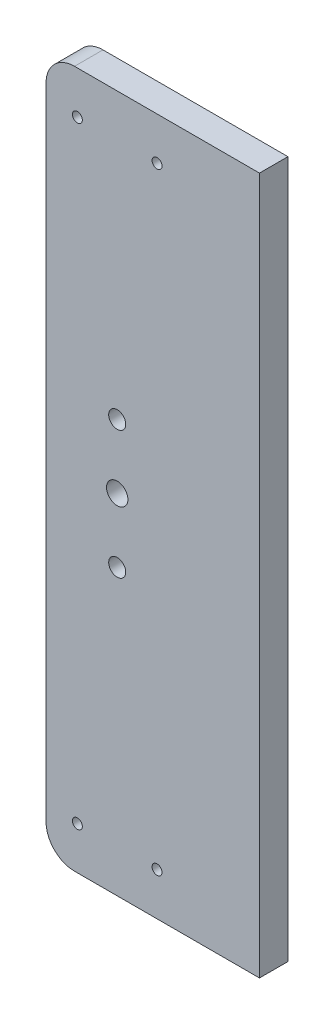
SolidWorks part; units mm, degrees
material "Органическое стекло СО-95-К ГОСТ 10667-90"
ref_plane "Спереди" through (0, 0, 0) normal (0, 0, 1) x (1, 0, 0)
ref_plane "Сверху" through (0, 0, 0) normal (0, 1, 0) x (1, 0, 0)
ref_plane "Справа" through (0, 0, 0) normal (1, 0, 0) x (0, 0, -1)
ref_axis "ОсьX" through (-88.99, 0, 0) along (1, 0, 0)
ref_axis "ОсьZ" through (0, 55, 0) along (0, -1, 0)
ref_axis "ОсьY" through (0, 0, -88.99) along (0, 0, 1)
sketch "Эскиз1" plane through (0, 0, 0) normal (0, 0, 1) x (1, 0, 0)
  line L0 (0, 0) -> (0, 59.9562) construction
  line L1 (-50, 245) -> (100, 245)
  line L3 (-50, -245) -> (100, -245)
  line L4 (100, 245) -> (100, -245)
  line L7 (100, 245) -> (100, -245)
  line L8 (-109.4093, 0) -> (100, 0) construction
  line L9 (-50, 245) -> (-50, -245)
  circle A0 centre (-28, 215) radius 3.5
  circle A16 centre (28, 215) radius 3.5
  circle A17 centre (28, -215) radius 3.5
  circle A18 centre (-28, -215) radius 3.5
  circle A23 centre (0, 0) radius 7.5
  circle A24 centre (0, 45) radius 6
  circle A25 centre (0, -45) radius 6
  dimension "D3" = 7
  dimension "D4" = 430
  dimension "D5" = 56
  dimension "D6" = 100
  dimension "D8" = 150
  dimension "D11" = 90
  dimension "D12" = 12
  dimension "D13" = 15
  dimension "D2" = 490
extrude "Бобышка-Вытянуть1" add sketch "Эскиз1" along normal blind 20 contours L4 L1 L3 A18 A16 A0 region at (25.1908, 0, 0)
fillet "Скругление1" radius 20 2 edges at (-50, 245, 10) (-50, -245, 10)
